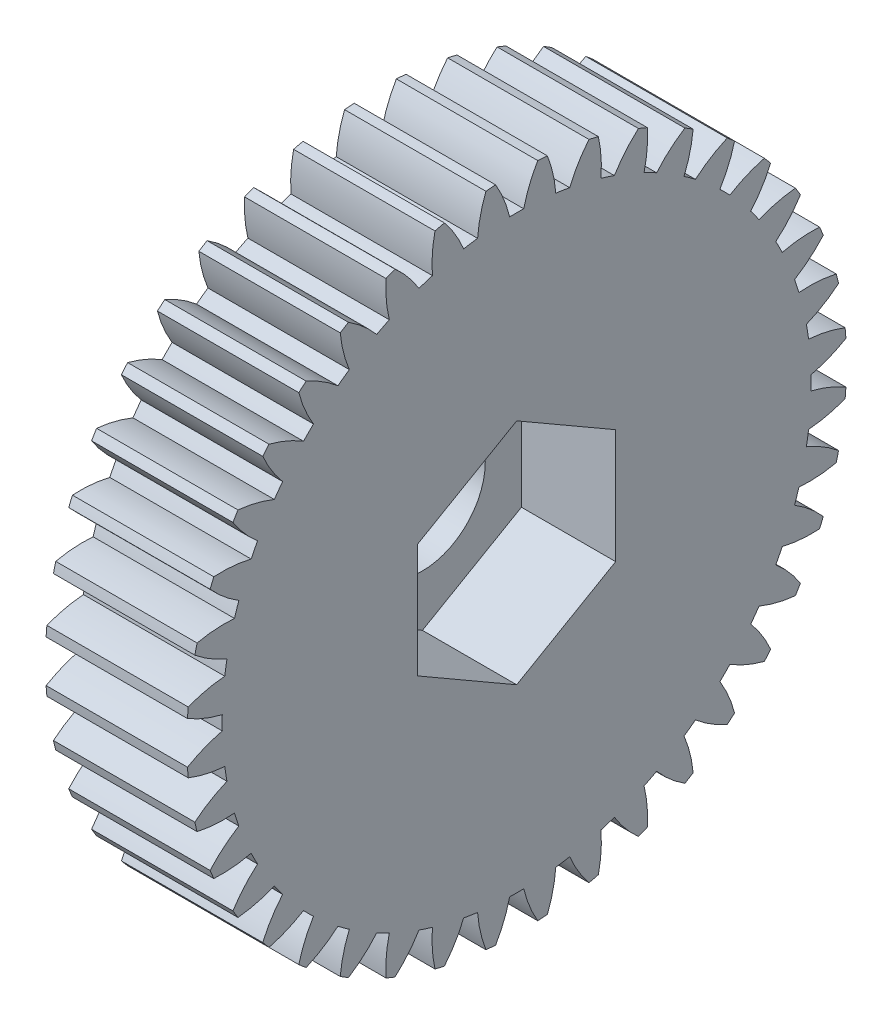
SolidWorks part; units mm, degrees
ref_plane "Plane1" through (0, 0, 0) normal (0, 0, 1) x (1, 0, 0)
ref_plane "Plane2" through (0, 0, 0) normal (0, 1, 0) x (1, 0, 0)
ref_plane "Plane3" through (0, 0, 0) normal (1, 0, 0) x (0, 0, -1)
sketch "HoldingSke" plane through (0, 0, 0) normal (0, 1, 0) x (1, 0, 0)
  line L0 (0, 0) -> (0.766, -0.6428)
  line L1 (-15, 0) -> (100, 0) construction
  line L2 (0, 0) -> (-2.1039, 2.3779)
  line L3 (0, 0) -> (-11.863, 4.5341)
  line L4 (0, 0) -> (6.6156, 5.5511)
  line L5 (0, 0) -> (-46.8476, -17.4728)
  line L6 (0, 0) -> (-7.4607, -5.0337)
  line L7 (-2.1039, 2.3779) -> (8.6586, 51.2059)
  line L8 (-76.2, 54.61) -> (-75.5, 54.61)
  line L9 (-71.009, 38.7566) -> (-53.1078, 45.2721)
  line L10 (-76.2, 71.12) -> (104.1128, 71.12)
  line L11 (0, 0) -> (-9, 0)
  line L12 (-76.2, 101.6) -> (-76.162, 101.6)
  line L13 (24.9733, 27.94) -> (52.9518, 28.4284)
  line L14 (24.9733, 27.94) -> (24.9743, 27.94)
  line L15 (24.9733, 27.94) -> (100.4006, 29.5858)
  line L16 (-63.627, -1) -> (-12.827, -1)
  circle A0 centre (0, 0) radius 2
  circle A1 centre (0, 0) radius 18.749
  circle A2 centre (0, 0) radius 37.5
  circle A3 centre (0, 0) radius 2
  dimension "MHD" = 37.498
  dimension "Hub_dia" = 75
  dimension "Bore" = 4
  dimension "MBD" = 4
  dimension "Num_teeth" = 40
  dimension "Pitch" = 1
  dimension "Overall_len" = 50
  dimension "Show_teeth" = 40
  dimension "Thickness" = 9
  dimension "OAL" = 50.0001
  dimension "T_dim" = 0.7
  dimension "Ap" = 20
  dimension "H" = 19.05
  dimension "Pitch_radius" = 180.3128
  dimension "Width" = 9
  dimension "Backlash" = 0.038
  dimension "Addendum_fac" = 1
  dimension "Dedendum_fac" = 1.25
  dimension "Clearance_fac" = 0.25
  dimension "Dedendum_add" = 0.001
  dimension "Module" = 1
sketch "BasProSke" plane through (0, 0, 0) normal (0, 1, 0) x (1, 0, 0)
  line L0 (-10, 0) -> (60, 0) construction
  line L1 (0, 0) -> (0, 21)
  line L2 (0, 0) -> (9, 0)
  line L3 (9, 0) -> (9, 21)
  line L4 (9, 21) -> (0, 21)
  dimension "Thickness" = 9
  dimension "Diameter" = 42
revolve "Base-Revolve" add sketch "BasProSke" angle 360 about L0
sketch "TooCutSke" plane through (0, 0, 0) normal (1, 0, 0) x (0, 0, -1)
  line L1 (0, 0) -> (0, 107) construction
  line L2 (0, 0) -> (-0.8517, 19.9819) construction
  line L3 (0, 0) -> (-3.1363, 39.8509) construction
  line L4 (-0.8517, 19.9819) -> (-1.5682, 19.9255) construction
  arc A0 (0.4487, 18.7436) -> (-0.4487, 18.7436) centre (0, 0) ccw
  arc A1 (1.3547, 20.9817) -> (-1.3547, 20.9817) centre (0, 0) ccw
  circle A2 centre (0, 0) radius 20 construction
  circle A3 centre (0, 0) radius 18.7939 construction
  arc A4 (-0.4487, 18.7436) -> (-1.3547, 20.9817) centre (-8.2322, 16.895) ccw
  arc A5 (1.3547, 20.9817) -> (0.4487, 18.7436) centre (8.2322, 16.895) ccw
  dimension "Root_dia" = 37.498
  dimension "Overcut_dia" = 42.0508
  dimension "Pitch_dia" = 40
  dimension "Base_dia" = 37.5877
  dimension "Flank_rad" = 8
  dimension "Half_ang" = 4.5
  dimension "Half_CT" = 0.7187
extrude "ToothCut" cut sketch "TooCutSke" along normal through all
fillet "Breaks" [suppressed] radius 0.02 tangent propagation no
fillet "RootFillets" [suppressed] radius 0.251
pattern_circular "TeethCuts" count 40 every 9 about axis through (-10, 0, 0) along (1, 0, 0) of "ToothCut", "RootFillets", "Breaks"
sketch "HubNeaOneSke" plane through (0, 0, 0) normal (-1, 0, 0) x (0, 0, 1)
  circle A0 centre (0, 0) radius 18.749
  dimension "Diameter" = 37.498
extrude "HubNearOne" [suppressed] add sketch "HubNeaOneSke" along normal blind 41.0001
sketch "HubNeaBotSke" plane through (0, 0, 0) normal (-1, 0, 0) x (0, 0, 1)
  circle A0 centre (0, 0) radius 18.749
  dimension "Diameter" = 37.498
extrude "HubNearBoth" [suppressed] add sketch "HubNeaBotSke" along normal blind 20.5
ref_plane "FarPln" through (9, 0, 0) normal (1, 0, 0) x (0, 0, -1)
sketch "HubFarSke" plane through (9, 0, 0) normal (1, 0, 0) x (0, 0, -1)
  circle A0 centre (0, 0) radius 18.749
  dimension "Diameter" = 37.498
extrude "HubFar" [suppressed] add sketch "HubFarSke" along normal blind 20.5
sketch "BorSke" plane through (0, 0, 0) normal (1, 0, 0) x (0, 0, -1)
  circle A0 centre (0, 0) radius 2
  dimension "Diameter" = 4
extrude "Bore" cut sketch "BorSke" along normal mid plane 100.0001
sketch "KeySke" plane through (0, 0, 0) normal (1, 0, 0) x (0, 0, -1)
  line L0 (-0.8, 0) -> (-0.8, 2.7)
  line L1 (-0.8, 2.7) -> (0.8, 2.7)
  line L2 (0.8, 2.7) -> (0.8, 0)
  line L3 (0, 0) -> (0, 34) construction
  line L4 (-0.8, 0) -> (0.8, 0)
  dimension "Offset" = 2.7
  dimension "Width" = 1.6
extrude "Keyway" [suppressed] cut sketch "KeySke" along normal mid plane 100.0001
pattern_circular "Keyway2" [suppressed] count 2 every 90 about axis through (-10, 0, 0) along (1, 0, 0)
sketch "Sketch1" plane through (9, 0, 0) normal (1, 0, 0) x (0, 0, -1)
  line L1 (0, 7.2746) -> (-6.3, 3.6373)
  line L2 (-6.3, 3.6373) -> (-6.3, -3.6373)
  line L3 (-6.3, -3.6373) -> (0, -7.2746)
  line L4 (0, -7.2746) -> (6.3, -3.6373)
  line L5 (6.3, -3.6373) -> (6.3, 3.6373)
  line L6 (6.3, 3.6373) -> (0, 7.2746)
  circle A0 centre (0, 0) radius 7.2746
  circle A2 centre (0, 0) radius 6.3 construction
  circle A3 centre (0, 0) radius 4
  dimension "D1" = 8
  dimension "D2" = 12.6
extrude "Cut-Extrude1" cut sketch "Sketch1" against normal blind 6 contours L1 L2 L3 L4 L5 L6
extrude "Cut-Extrude2" cut sketch "Sketch1<7>" against normal through all contours A3 region at (9, 0, 0)
sketch "Sketch1<7>" plane through (9, 0, 0) normal (1, 0, 0) x (0, 0, -1) same geometry as "Sketch1"
sketch "Sketch2" plane through (0, 0, 0) normal (-1, 0, 0) x (0, 0, 1)
  circle A0 centre (0, 0) radius 6
  circle A1 centre (0, 0) radius 4
  dimension "D1" = 12
  dimension "D2" = 8
extrude "Boss-Extrude1" add sketch "Sketch2" along normal blind 1.8
sketch "Sketch3" plane through (3, 0, 0) normal (1, 0, 0) x (0, 0, -1)
  line L1 (4, 4) -> (-4, 4)
  line L2 (4, 4) -> (4, -4)
  line L3 (4, -4) -> (-4, -4)
  line L4 (-4, 4) -> (-4, -4)
  line L6 (5.5, 5.5) -> (5.5, -5.5)
  line L7 (5.5, -5.5) -> (-5.5, -5.5)
  line L8 (-5.5, 5.5) -> (-5.5, -5.5)
  line L9 (5.5, 5.5) -> (-5.5, 5.5)
  line L10 (5.5, 4) -> (5.6718, 4)
  line L11 (6.3, 3.6373) -> (0, 7.2746) construction
  line L12 (5.5, -4) -> (5.6718, -4)
  line L13 (0, -7.2746) -> (6.3, -3.6373) construction
  line L14 (-5.5, -4) -> (-5.6718, -4)
  line L15 (-6.3, -3.6373) -> (0, -7.2746) construction
  line L16 (-5.5, 4) -> (-5.6718, 4)
  line L17 (0, 7.2746) -> (-6.3, 3.6373) construction
  circle A0 centre (0, 0) radius 4 construction
  line M10 (6.3, 3.6373) -> (0, 7.2746)
  line M11 (0, 7.2746) -> (-6.3, 3.6373)
  line M13 (-6.3, -3.6373) -> (0, -7.2746)
  line M14 (0, -7.2746) -> (6.3, -3.6373)
  dimension "D1" = 1.5
extrude "Boss-Extrude2" [suppressed] add sketch "Sketch3" along normal blind 0.3 contours L9 L8 L7 L6 L4 L1 L2 L3 M10 M11 M13 M14 | L12 L6 M14 | L6 L10 M10 | L16 L8 M11 | L8 L14 M13
equation "' \"Module@HoldingSke\" = 6.35"
equation "' \"Num_teeth@HoldingSke\" = 12"
equation "' \"Ap@HoldingSke\" =  20"
equation "' \"Ap@HoldingSke\" = 20"
equation "' \"Width@HoldingSke\" = 0.5 * 25.4"
equation "' \"Hub_dia@HoldingSke\"= 1 * 25.4"
equation "' \"Hub_dia@HoldingSke\" = 1 * 25.4"
equation "' \"Overall_len@HoldingSke\" = 1.0 * 25.4"
equation "' \"Bore@HoldingSke\" = 0.75 * 25.4"
equation "' \"T_dim@HoldingSke\" = 0.1 * 25.4"
equation "' \"Width@KeySke\" = 0.25 * 25.4"
equation "' \"Show_teeth@HoldingSke\" = 13"
equation "' \"Backlash@HoldingSke\" = 0.009 * 25.4"
equation "' \"Addendum_fac@HoldingSke\" = 1.0"
equation "' \"Dedendum_fac@HoldingSke\" = 1.25"
equation "' \"Dedendum_add@HoldingSke\" = 0.00005 * 25.4"
equation "' \"Clearance_fac@HoldingSke\" = 0.25"
equation "\"Pitch@HoldingSke\" = 1 / \"Module@HoldingSke\""
equation "\"Overcut_dia@TooCutSke\" = (\"Num_teeth@HoldingSke\" + 2 * \"Addendum_fac@HoldingSke\") / \"Pitch@HoldingSke\" + 0.002 * 25.4"
equation "\"Pitch_dia@TooCutSke\" = \"Num_teeth@HoldingSke\" / \"Pitch@HoldingSke\""
equation "\"Base_dia@TooCutSke\" = \"Num_teeth@HoldingSke\" / \"Pitch@HoldingSke\" * cos((\"Ap@HoldingSke\"  * 3.14159265 / 180))"
equation "\"Root_dia@TooCutSke\" = (\"Num_teeth@HoldingSke\" + 2) / \"Pitch@HoldingSke\" - 2 * (\"Addendum_fac@HoldingSke\" + \"Dedendum_fac@HoldingSke\") / \"Pitch@HoldingSke\" - \"Dedendum_add@HoldingSke\" * 2"
equation "\"Half_ang@TooCutSke\" = 180 / \"Num_teeth@HoldingSke\""
equation "\"Half_CT@TooCutSke\" = \"Num_teeth@HoldingSke\" / \"Pitch@HoldingSke\" * sin((3.14159265 / 2 / \"Num_teeth@HoldingSke\")) / 2 - 7 * \"Backlash@HoldingSke\" / 4"
equation "\"Flank_rad@TooCutSke\" = \"Num_teeth@HoldingSke\" / \"Pitch@HoldingSke\" / 5"
equation "\"Radius@RootFillets\" = \"Clearance_fac@HoldingSke\" / \"Pitch@HoldingSke\" + \"Dedendum_add@HoldingSke\""
equation "\"Break_rad@Breaks\" = 0.02 / \"Pitch@HoldingSke\""
equation "\"Thickness@HoldingSke\" = \"Width@HoldingSke\""
equation "\"OAL@HoldingSke\" = \"Thickness@HoldingSke\""
equation "\"MHD@HoldingSke\" = (\"Num_teeth@HoldingSke\" + 2) / \"Pitch@HoldingSke\" - 2 * (\"Addendum_fac@HoldingSke\" + \"Dedendum_fac@HoldingSke\")  / \"Pitch@HoldingSke\" - \"Dedendum_add@HoldingSke\" * 2"
equation "\"MBD@HoldingSke\" = (\"Num_teeth@HoldingSke\" + 2) / \"Pitch@HoldingSke\" - 2 * (\"Addendum_fac@HoldingSke\" + \"Dedendum_fac@HoldingSke\")  / \"Pitch@HoldingSke\" - \"Dedendum_add@HoldingSke\" * 2 - 0.002 * 25.4"
equation "\"MHD@HoldingSke\" = ((sgn( \"MHD@HoldingSke\" - \"Hub_dia@HoldingSke\" )-1)*( \"MHD@HoldingSke\" - \"Hub_dia@HoldingSke\" ))/-2+ \"Hub_dia@HoldingSke\""
equation "\"MBD@HoldingSke\" = ((sgn( \"MBD@HoldingSke\" - \"Bore@HoldingSke\" )-1)*( \"MBD@HoldingSke\" - \"Bore@HoldingSke\" ))/-2+ \"Bore@HoldingSke\""
equation "\"OAL@HoldingSke\" = ((sgn( \"OAL@HoldingSke\" - \"Overall_len@HoldingSke\" )+1)*( \"OAL@HoldingSke\" - \"Overall_len@HoldingSke\" ))/2 + \"Overall_len@HoldingSke\" + 0.000002 * 25.4"
equation "\"Num_teeth@TeethCuts\" = int( \"Show_teeth@HoldingSke\" ) + 1"
equation "\"Num_teeth@TeethCuts\" = ((sgn( \"Num_teeth@TeethCuts\" - \"Num_teeth@HoldingSke\" )-1)*( \"Num_teeth@TeethCuts\" - \"Num_teeth@HoldingSke\" ))/-2+ \"Num_teeth@HoldingSke\""
equation "\"Num_teeth@TeethCuts\" = ((sgn( \"Num_teeth@TeethCuts\" - 2.0)+1)*( \"Num_teeth@TeethCuts\" - 2.0))/2 +2.0"
equation "\"Angle@TeethCuts\" = 360.0 / \"Num_teeth@HoldingSke\""
equation "\"Diameter@BasProSke\" = (\"Num_teeth@HoldingSke\" + 2 * \"Addendum_fac@HoldingSke\") / \"Pitch@HoldingSke\""
equation "\"Thickness@BasProSke\"  = \"Thickness@HoldingSke\""
equation "' \"Fillet_rad@BasProSke\" =  \"Thickness@HoldingSke\" * 0.05"
equation "' \"Fillet_rad@BasProSke\" = \"Thickness@HoldingSke\" * 0.05"
equation "\"MHD@HoldingSke\" = ((sgn( \"MHD@HoldingSke\" - \"Root_dia@TooCutSke\" )-1)*( \"MHD@HoldingSke\" - \"Root_dia@TooCutSke\" ))/-2+ \"Root_dia@TooCutSke\""
equation "\"Diameter@HubNeaOneSke\" = \"MHD@HoldingSke\""
equation "\"Length@HubNearOne\" = \"OAL@HoldingSke\" - \"Thickness@BasProSke\""
equation "\"Diameter@HubNeaBotSke\" = \"MHD@HoldingSke\""
equation "\"Length@HubNearBoth\" = ( \"OAL@HoldingSke\" - \"Thickness@BasProSke\" ) / 2.0"
equation "\"Thickness@FarPln\" = \"Thickness@BasProSke\""
equation "\"Diameter@HubFarSke\" = \"MHD@HoldingSke\""
equation "\"Length@HubFar\" = ( \"OAL@HoldingSke\" - \"Thickness@BasProSke\" ) / 2.0"
equation "\"Diameter@BorSke\" = \"MBD@HoldingSke\""
equation "\"D1@Bore\" = \"OAL@HoldingSke\" * 2.0"
equation "\"D1@Keyway\" = \"OAL@HoldingSke\" * 2.0"
equation "\"Offset@KeySke\" = \"T_dim@HoldingSke\" + \"MBD@HoldingSke\" / 2.0"
